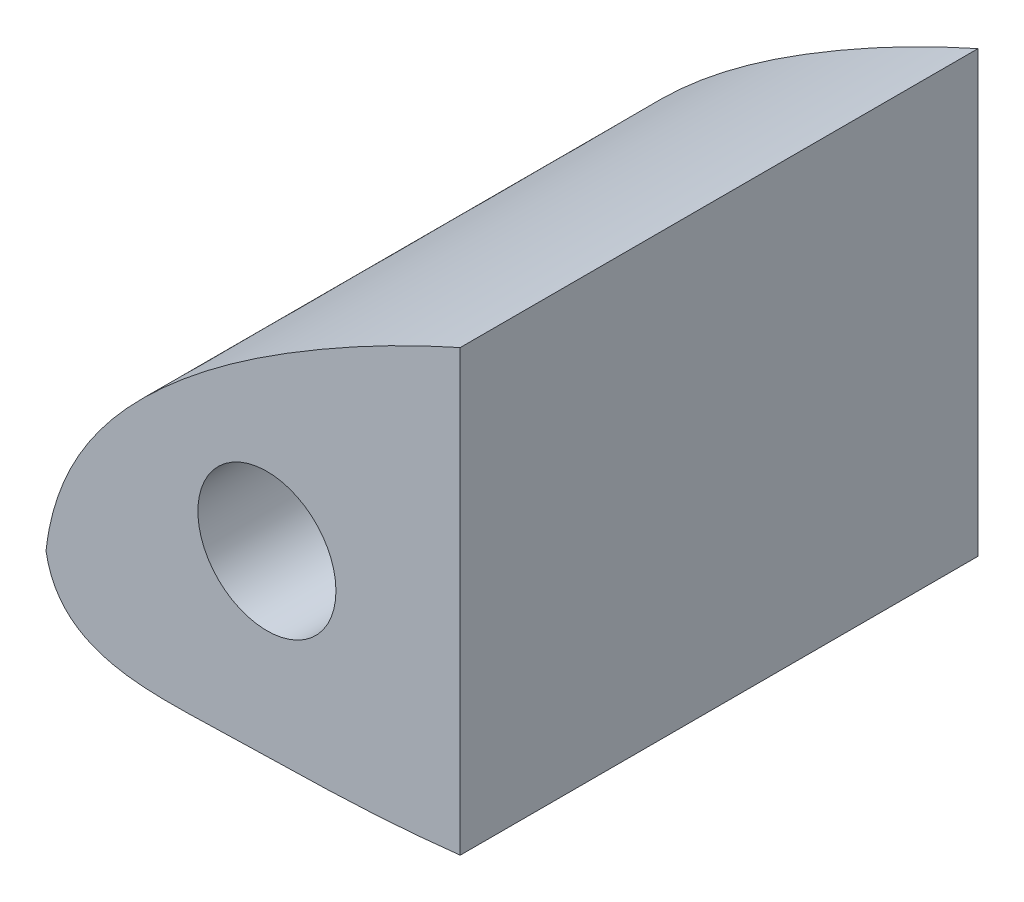
SolidWorks part; units mm, degrees
ref_plane "Front Plane" through (0, 0, 0) normal (0, 0, 1) x (1, 0, 0)
ref_plane "Top Plane" through (0, 0, 0) normal (0, 1, 0) x (1, 0, 0)
ref_plane "Right Plane" through (0, 0, 0) normal (1, 0, 0) x (0, 0, -1)
sketch "Sketch1" plane through (0, 0, 0) normal (0, 0, 1) x (1, 0, 0)
  spline S0 degree 3 poles (0.0006, 0.0001) (0.8106, 7.3592) (8.6491, 17.8566) (26.2867, 29.9752) (52.1111, 42.0692) (89.5976, 49.2908) (131.4008, 47.8848) (173.2567, 40.0411) (217.9611, 29.613) (256.9521, 19.5289) (290.3598, 8.711) (301.2732, 4.3828) (314.8169, -0.5162) (309.8463, 0.0001) knots 0 0 0 0 0.060864 0.113688 0.188609 0.312909 0.448482 0.557612 0.691544 0.852438 0.929756 0.976058 1 1 1 1
  spline S1 degree 3 poles (309.8463, 0.0001) (303.9568, 1.471) (293.9895, 2.094) (276.264, 4.5144) (260.8463, 5.4274) (235.8588, 7.8703) (205.1014, 8.8381) (157.7186, 9.0307) (110.4973, 6.1815) (66.5062, -0.5867) (36.4547, -6.0985) (15.3166, -6.1891) (1.2307, -6.9241) (0.0006, 0.0001) knots 0 0 0 0 0.057787 0.095275 0.171021 0.205339 0.335319 0.464904 0.658702 0.785512 0.893517 0.943092 1 1 1 1
extrude "Boss-Extrude1" add sketch "Sketch1" along normal blind 47.625
sketch "Sketch2" plane through (0, 0, 47.625) normal (0, 0, 1) x (1, 0, 0)
  circle A0 centre (20.32, 10.16) radius 6.35
  circle A1 centre (227.2963, 19.0501) radius 3.175
  dimension "D2" = 12.7
  dimension "D3" = 6.35
  dimension "D6" = 20.32
  dimension "D1" = 82.55
  dimension "D4" = 19.05
  dimension "D5" = 10.16
extrude "Cut-Extrude1" cut sketch "Sketch2" against normal through all
sketch "Sketch3" plane through (0, 0, 47.625) normal (0, 0, 1) x (1, 0, 0)
  line L1 (38.1, 71.718) -> (331.2889, 71.718)
  line L2 (38.1, 71.718) -> (38.1, -66.2532)
  line L3 (38.1, -66.2532) -> (331.2889, -66.2532)
  line L4 (331.2889, 71.718) -> (331.2889, -66.2532)
  dimension "D1" = 38.1
extrude "Cut-Extrude2" cut sketch "Sketch3" against normal through all
